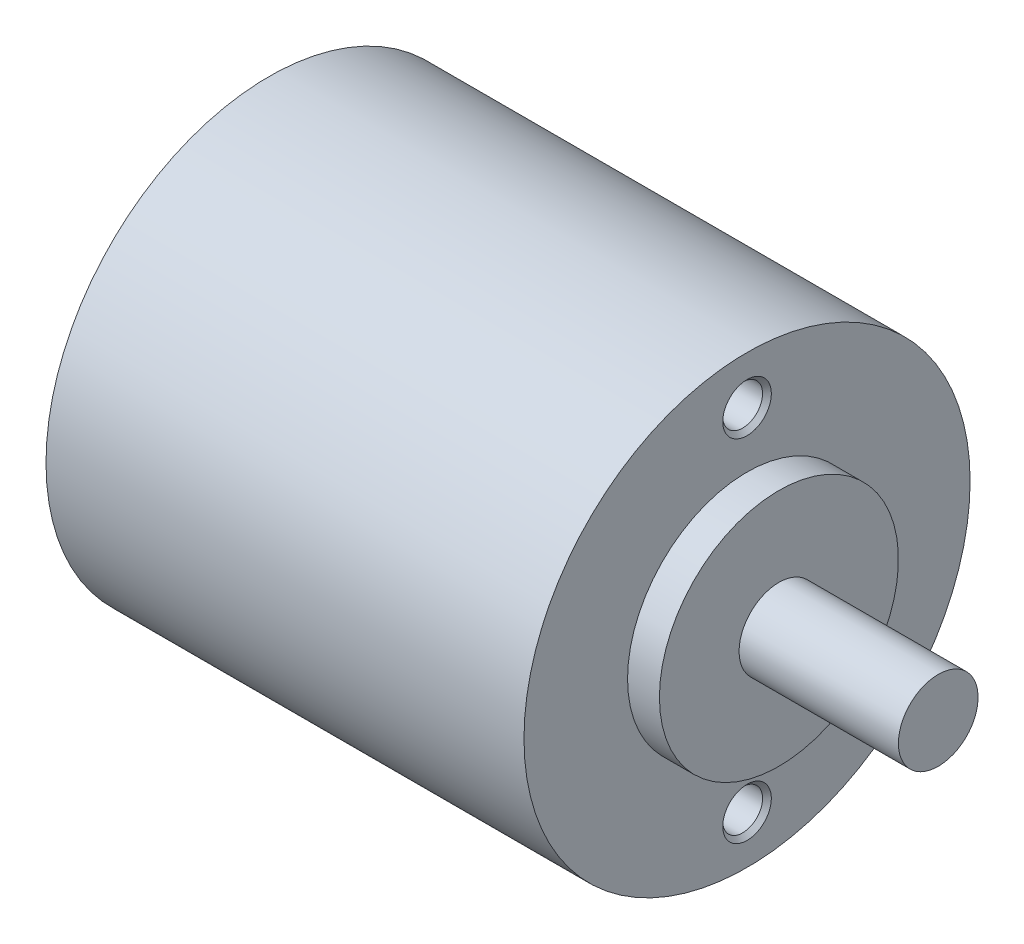
SolidWorks part; units mm, degrees
ref_plane "Plan de face" through (0, 0, 0) normal (0, 0, 1) x (1, 0, 0)
ref_plane "Plan de dessus" through (0, 0, 0) normal (0, 1, 0) x (1, 0, 0)
ref_plane "Plan de droite" through (0, 0, 0) normal (1, 0, 0) x (0, 0, -1)
sketch "Esquisse1" plane through (0, 0, 0) normal (0, 0, 1) x (1, 0, 0)
  line L0 (-51.1551, 0) -> (25.063, 0) construction
  line L1 (12, 2.5) -> (12, 0)
  line L2 (12, 0) -> (-30, 0)
  line L3 (-30, 0) -> (-30, 14)
  line L4 (-30, 14) -> (0, 14)
  line L5 (0, 14) -> (0, 7.5)
  line L6 (2, 2.5) -> (12, 2.5)
  line L7 (0, 7.5) -> (2, 7.5)
  line L8 (2, 7.5) -> (2, 2.5)
  dimension "D1" = 28
  dimension "D2" = 5
  dimension "D3" = 12
  dimension "D4" = 30
  dimension "D5" = 2
  dimension "D6" = 15
revolve "Révolution1" add sketch "Esquisse1" angle 360 about L0
hole_wizard "Trou taraudé M3x0.51" positions "Esquisse4" profile "Esquisse3" tap size "M3x0.5" standard "Ansi Metric"
sketch "Esquisse4" plane through (0, 0, 0) normal (1, 0, 0) x (0, 0, -1)
  circle A0 centre (0, 0) radius 11 construction
  point P0 (0, 11)
  point P2 (0, -11)
  dimension "D1" = 22
sketch "Esquisse3" plane through (0, 11, 0) normal (0, 1, 0) x (0, 0, -1)
  line L0 (0, 0) -> (0, 9.2511)
  line L1 (0, 9.2511) -> (1.25, 8.5)
  line L2 (1.25, 8.5) -> (1.25, 0.275)
  line L3 (1.25, 0.275) -> (1.525, 0)
  line L5 (1.525, 0) -> (0, 0)
  line L6 (-1.25, 0.275) -> (-1.525, 0) construction
  line L10 (0, 9.2511) -> (-1.25, 8.5) construction
  line L11 (0, -6.35) -> (0, 107.95) construction
  dimension "Diamètre du trou pour taraudage" = 2.5
  dimension "Profondeur du trou pour taraudage" = 8.5
  dimension "Diamètre du fraisage entrant" = 3.05
  dimension "Angle du fraisage entrant" = 90
  dimension "Angle de pointe" = 118
cosmetic thread "Filetage de perçage1" parameters "D1"=6, "D2"=3
cosmetic thread "Filetage de perçage2" parameters "D1"=6, "D2"=3
